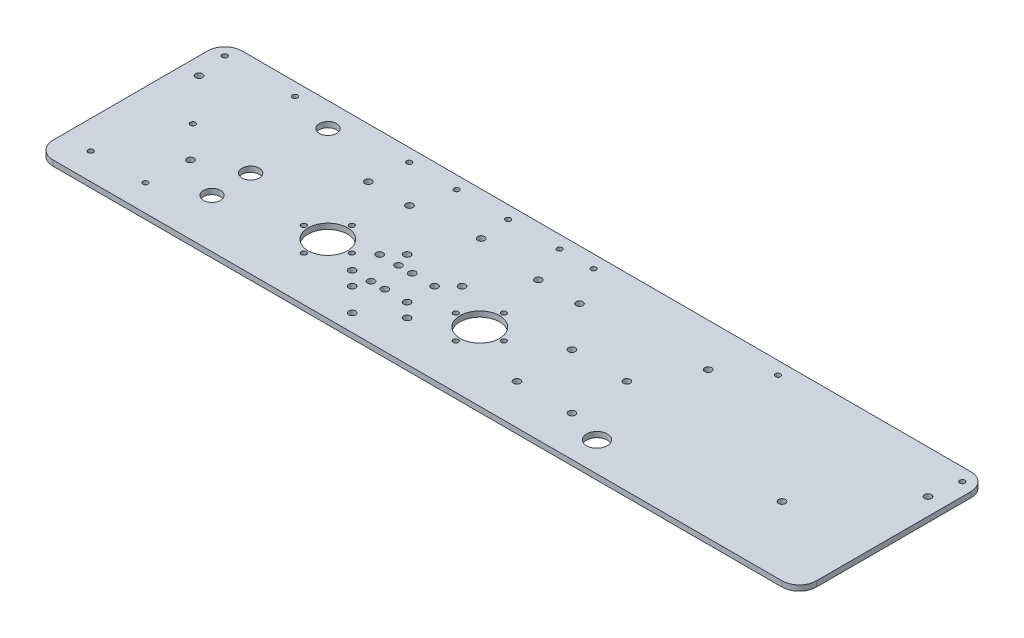
SolidWorks part; units mm, degrees
ref_plane "Front" through (0, 0, 0) normal (0, 0, 1) x (1, 0, 0)
ref_plane "Top" through (0, 0, 0) normal (0, 1, 0) x (1, 0, 0)
ref_plane "Right" through (0, 0, 0) normal (1, 0, 0) x (0, 0, -1)
sketch "Sketch1" plane through (0, 0, 0) normal (0, 1, 0) x (1, 0, 0)
  line L0 (-26.7996, 0) -> (-26.7996, 40)
  line L1 (-26.7996, 0) -> (417.7004, 0)
  line L2 (-26.7996, 0) -> (-26.7996, 110)
  line L3 (-26.7996, 110) -> (417.7004, 110)
  line L4 (417.7004, 0) -> (417.7004, 110)
  line L5 (-26.7996, 40) -> (23.2004, 40)
  line L6 (417.7004, 0) -> (417.7004, 40)
  line L7 (417.7004, 40) -> (367.7004, 40)
  line L8 (23.2004, 40) -> (103.2004, 40)
  line L9 (367.7004, 40) -> (191.7004, 40)
  line L10 (-26.7996, 110) -> (-26.7996, 85)
  line L11 (-26.7996, 85) -> (417.7004, 85)
  line L12 (-26.7996, 85) -> (-16.7996, 85)
  line L13 (417.7004, 85) -> (407.7004, 85)
  line L14 (103.2004, 40) -> (191.7004, 40)
  line L15 (147.4504, 40) -> (147.4504, 85)
  line L16 (279.7004, 40) -> (279.7004, 85)
  line L17 (147.4504, 40) -> (147.4504, 10)
  line L18 (-26.7996, 110) -> (-26.7996, 102.5)
  line L19 (-26.7996, 102.5) -> (417.7004, 102.5)
  line L20 (-26.7996, 102.5) -> (-19.2996, 102.5)
  line L21 (417.7004, 102.5) -> (410.2004, 102.5)
  line L22 (195.4504, 102.5) -> (410.2004, 102.5)
  line L23 (-19.2996, 102.5) -> (195.4504, 102.5)
  line L24 (417.7004, 0) -> (417.7004, 17.2282)
  line L25 (417.7004, 17.2282) -> (282.7004, 17.2282)
  circle A10 centre (367.7004, 40) radius 2
  circle A11 centre (23.2004, 40) radius 2
  circle A12 centre (103.2004, 40) radius 11.5
  circle A13 centre (103.2004, 40) radius 14
  circle A15 centre (103.2004, 54) radius 1.5
  circle A16 centre (89.2004, 40) radius 1.5
  circle A17 centre (103.2004, 26) radius 1.5
  circle A18 centre (117.2004, 40) radius 1.5
  circle A19 centre (191.7004, 40) radius 11.5
  circle A20 centre (191.7004, 40) radius 14
  circle A21 centre (191.7004, 26) radius 1.5
  circle A22 centre (205.7004, 40) radius 1.5
  circle A23 centre (191.7004, 54) radius 1.5
  circle A24 centre (177.7004, 40) radius 1.5
  circle A25 centre (-16.7996, 85) radius 2
  circle A26 centre (407.7004, 85) radius 2
  circle A27 centre (147.4504, 85) radius 2
  circle A28 centre (279.7004, 85) radius 2
  circle A29 centre (147.4504, 10) radius 2
  circle A30 centre (195.4504, 102.5) radius 1.5
  circle A31 centre (-19.2996, 102.5) radius 1.5
  circle A32 centre (410.2004, 102.5) radius 1.5
  circle A33 centre (302.8254, 102.5) radius 1.5
  circle A34 centre (88.0754, 102.5) radius 1.5
  circle A35 centre (282.7004, 17.2282) radius 6
  dimension "D3" = 40
  dimension "D7" = 80
  dimension "D8" = 176
  dimension "D9" = 25
  dimension "D11" = 10
  dimension "D12" = 30
  dimension "D13" = 7.5
  dimension "D14" = 7.5
  dimension "D16" = 17.2282
  dimension "D1" = 110
  dimension "D2" = 444.5
  dimension "D4" = 50
  dimension "D5" = 40
  dimension "D6" = 50
  dimension "D10" = 10
  dimension "D15" = 7.5
  dimension "D17" = 135
extrude "Boss-Extrude1" add sketch "Sketch1" along normal blind 3.175 contours A18 L14 A12 L8 A16 A13 A17 | A18 A13 A15 A16 L8 A12 L14 | A24 L14 A19 L9 A22 A20 A23 | A24 A20 A21 A22 L9 A19 L14 | A29 L14 A18 A13 A17 A16 L8 A11 L5 L0 L1 L4 L7 A10 L9 A22 A20 A21 A24 | A28 L11 A27 L15 L14 A24 A20 A23 A22 L9 L16 | A27 L11 A25 L2 L5 A11 L8 A16 A13 A15 A18 L14 L15 | A28 L11 A26 L13 L4 L3 L2 A25 A27 | A28 L16 L9 A10 L7 L4 L13 A26 L11 | A34 L23 A30 L22 A33 A32 L21 L4 L3 L10 L19 A31 region at (196.684, 0, -19.4923) region at (58.5861, 0, -63.184) region at (195.421, 0, -93.7571) region at (195.4504, 0, -106.2666) region at (348.6559, 0, -62.489) region at (93.521, 0, -49.6794) region at (90.515, 0, -38.754) region at (214.7998, 0, -63.4004) region at (204.3858, 0, -41.246) region at (201.3798, 0, -30.3206)
fillet "Fillet1" radius 10 4 edges at (417.7004, 1.5875, -110) (417.7004, 1.5875, 0) (-26.7996, 1.5875, 0) (-26.7996, 1.5875, -110)
sketch "Sketch2" plane through (0, 3.175, 0) normal (0, 1, 0) x (1, 0, 0)
  line L0 (-26.7996, 55.4056) -> (36.2004, 55.4056)
  line L1 (-26.7996, 10) -> (-26.7996, 100) construction
  line L2 (36.2004, 55.4056) -> (76.2004, 55.4056)
  line L3 (-16.7996, 110) -> (407.7004, 110) construction
  line L4 (36.2004, 55.4056) -> (36.2004, 23.4056)
  line L5 (36.2004, 23.4056) -> (68.2004, 23.4056)
  line L6 (76.2004, 55.4056) -> (165.9504, 55.4056)
  line L7 (165.9504, 55.4056) -> (133.9504, 55.4056)
  line L8 (133.9504, 55.4056) -> (133.9504, 23.4056)
  line L9 (133.9504, 23.4056) -> (165.9504, 23.4056)
  line L10 (133.9504, 23.4056) -> (125.9504, 23.4056)
  line L11 (125.9504, 23.4056) -> (125.9504, 55.4056)
  line L12 (165.9504, 55.4056) -> (157.9504, 55.4056)
  line L13 (157.9504, 55.4056) -> (157.9504, 23.4056)
  line L14 (157.9504, 23.4056) -> (157.9504, 31.4056)
  line L15 (157.9504, 55.4056) -> (157.9504, 47.4056)
  line L16 (157.9504, 47.4056) -> (133.9504, 47.4056)
  circle A4 centre (133.9504, 55.4056) radius 2
  circle A5 centre (165.9504, 55.4056) radius 2
  circle A9 centre (133.9504, 23.4056) radius 2
  circle A10 centre (165.9504, 23.4056) radius 2
  circle A11 centre (157.9504, 31.4056) radius 2
  circle A12 centre (125.9504, 31.4056) radius 2
  circle A13 centre (125.9504, 47.4056) radius 2
  circle A14 centre (157.9504, 47.4056) radius 2
  dimension "D5" = 89.75
  dimension "D6" = 32
  dimension "D7" = 8
  dimension "D10" = 8
  dimension "D1" = 63
  dimension "D2" = 40
  dimension "D3" = 54.5944
  dimension "D4" = 32
  dimension "D8" = 8
  dimension "D9" = 8
extrude "Cut-Extrude1" cut sketch "Sketch2" against normal blind 10 contours A4 | A5 | A13 | A12 | A9 | A10 | A11 | A14
sketch "Sketch3" plane through (0, 0, 0) normal (0, -1, 0) x (1, 0, 0)
  line L0 (133.9504, -55.4056) -> (133.9504, -47.4056)
  line L1 (133.9504, -47.4056) -> (136.9504, -47.4056)
  line L2 (136.9504, -47.4056) -> (144.9504, -47.4056)
  line L3 (136.9504, -47.4056) -> (136.9504, -31.4056)
  line L4 (136.9504, -31.4056) -> (144.9504, -31.4056)
  line L5 (165.9504, -55.4056) -> (229.9504, -55.4056)
  line L6 (229.9504, -55.4056) -> (261.9504, -55.4056)
  line L7 (261.9504, -55.4056) -> (261.9504, -23.4056)
  line L8 (261.9504, -23.4056) -> (229.9504, -23.4056)
  circle A0 centre (144.9504, -47.4056) radius 2
  circle A1 centre (136.9504, -47.4056) radius 2
  circle A2 centre (144.9504, -31.4056) radius 2
  circle A3 centre (136.9504, -31.4056) radius 2
  circle A4 centre (261.9504, -55.4056) radius 2
  circle A5 centre (229.9504, -55.4056) radius 2
  circle A6 centre (261.9504, -23.4056) radius 2
  circle A7 centre (229.9504, -23.4056) radius 2
  dimension "D3" = 8
  dimension "D5" = 64
  dimension "D7" = 32
  dimension "D1" = 3
  dimension "D2" = 8
  dimension "D4" = 16
  dimension "D6" = 32
extrude "Cut-Extrude2" cut sketch "Sketch3" against normal blind 10 contours L2 A1 L1 | L1 A1 L2 | A2 | L4 A3 L3 | L3 A1 L1 | L3 A3 L4 | A0 | A4 | A6 | A7 | A5 region at (136.1016, 0, -46.5568) region at (144.9504, 0, -29.4622) region at (136.6675, 0, -31.1227) region at (137.7992, 0, -32.2544) region at (136.9504, 0, -48.2544) region at (137.7992, 0, -46.5568)
sketch "Sketch4" plane through (0, 3.175, 0) normal (0, 1, 0) x (1, 0, 0)
  circle A0 centre (21.5907, 102.5) radius 1.5
  circle A1 centre (5.6648, 58.9528) radius 1.5
  circle A2 centre (-10.261, 15.4056) radius 1.5
  circle A3 centre (47.3504, 50.9056) radius 2
  circle A4 centre (115.6708, 102.5) radius 1.5
  circle A5 centre (145.6708, 102.5) radius 1.5
  circle A6 centre (175.6708, 102.5) radius 1.5
  circle A7 centre (47.3504, 95.9056) radius 2
  circle A8 centre (21.5907, 15.4056) radius 1.5
  circle A9 centre (47.3504, 28.4056) radius 2
  circle A10 centre (208.9504, 80.8056) radius 2
  circle A11 centre (184.9504, 80.8056) radius 2
  circle A12 centre (109.9504, 80.8056) radius 2
  circle A13 centre (85.9504, 80.8056) radius 2
extrude "Cut-Extrude3" cut sketch "Sketch4" against normal blind 6.35
sketch "Sketch5" plane through (0, 3.175, 0) normal (0, 1, 0) x (1, 0, 0)
  circle A0 centre (47.3504, 95.9056) radius 5
  circle A1 centre (47.3504, 50.9056) radius 5
  circle A2 centre (47.3504, 28.4056) radius 5
extrude "Cut-Extrude4" cut sketch "Sketch5" against normal blind 3.175
